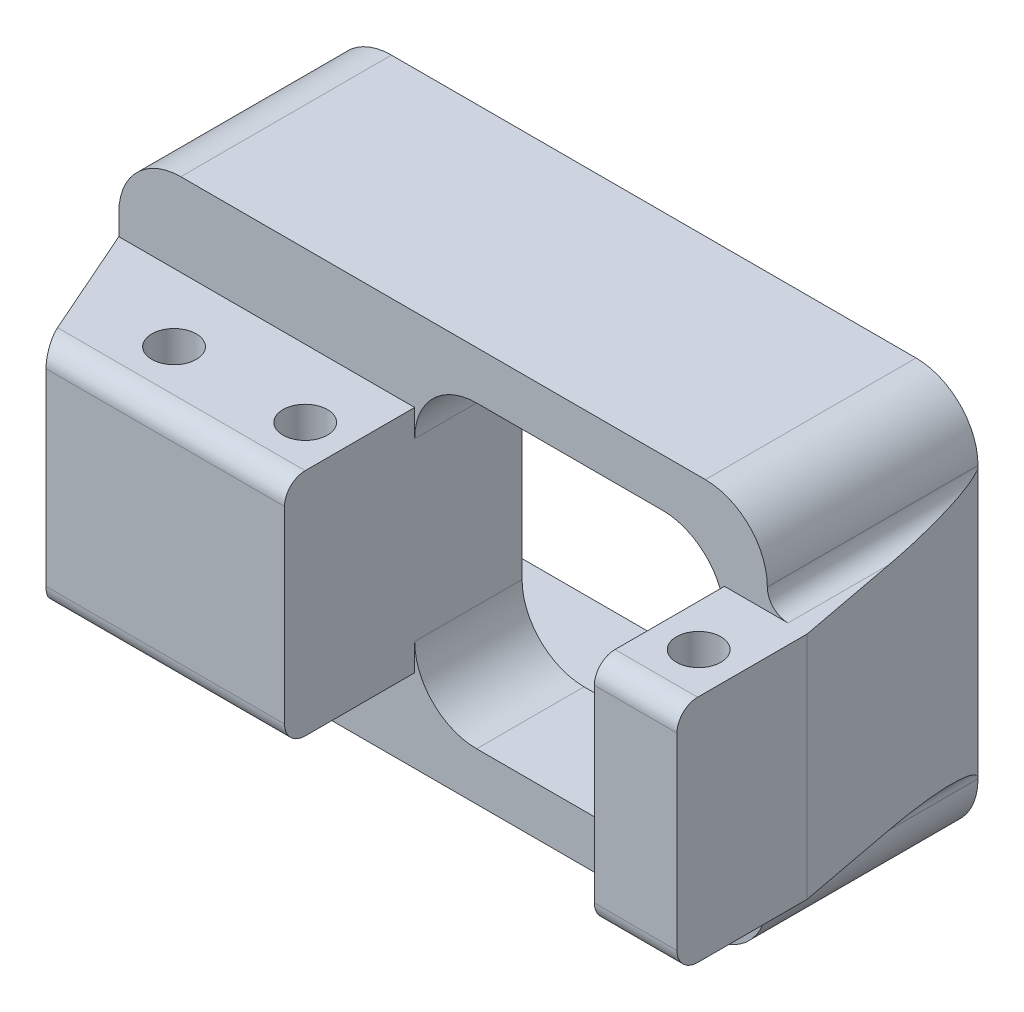
SolidWorks part; units mm, degrees
ref_plane "Front Plane" through (0, 0, 0) normal (0, 0, 1) x (1, 0, 0)
ref_plane "Top Plane" through (0, 0, 0) normal (0, 1, 0) x (1, 0, 0)
ref_plane "Right Plane" through (0, 0, 0) normal (1, 0, 0) x (0, 0, -1)
sketch "Sketch2" plane through (0, 0, 0) normal (0, 0, 1) x (1, 0, 0)
  line L1 (0, 0) -> (58, 0)
  line L2 (0, 0) -> (0, -33.5)
  line L3 (0, -33.5) -> (58, -33.5)
  line L4 (58, 0) -> (58, -33.5)
  line L5 (26.25, -2.25) -> (56.25, -2.25)
  line L6 (26.25, -2.25) -> (26.25, -31.25)
  line L7 (26.25, -31.25) -> (56.25, -31.25)
  line L8 (56.25, -2.25) -> (56.25, -31.25)
  line L9 (26.25, -2.25) -> (56.25, -31.25) construction
  line L10 (26.25, -31.25) -> (56.25, -2.25) construction
  line L11 (-2.4, 2.4) -> (60.4, 2.4)
  line L12 (-2.4, 2.4) -> (-2.4, -35.9)
  line L13 (-2.4, -35.9) -> (60.4, -35.9)
  line L14 (60.4, 2.4) -> (60.4, -35.9)
  circle A1 centre (16.2, -16.75) radius 4.25
  circle A2 centre (14.45, -16.75) radius 6
  circle A3 centre (14.45, -16.75) radius 6.5
  point P5 (41.25, -16.75)
  point P6 (41.25, -16.75)
  point P7 (16.2, -16.75)
  dimension "D9" = 8.5
  dimension "D10" = 12
  dimension "D15" = 13
  dimension "D16" = 1.75
  dimension "D1" = 33.5
  dimension "D2" = 58
  dimension "D3" = 16.75
  dimension "D4" = 16.75
  dimension "D5" = 16.2
  dimension "D6" = 16.75
  dimension "D7" = 30
  dimension "D8" = 29
  dimension "D11" = 2.4
  dimension "D12" = 2.4
  dimension "D13" = 2.4
  dimension "D14" = 2.4
extrude "Boss-Extrude1" add sketch "Sketch2" along normal blind 10 contours L14 L11 L12 L13 L1 L4 L3 L2 | L4 L1 L2 L3 A2 L5 L8 L7 L6 | A1 A2 | A3 A2 region at (29, -0.6698, 0) region at (29, 1.6644, 0) region at (8.6197, -16.75, 0) region at (8.1338, -16.75, 0)
extrude "Boss-Extrude2" add sketch "Sketch2<3>" against normal blind 10 contours L14 L11 L12 L13 L1 L4 L3 L2 region at (29, 1.6644, 0)
sketch "Sketch2<3>" plane through (0, 0, 0) normal (0, 0, 1) x (1, 0, 0) same geometry as "Sketch2"
extrude "Cut-Extrude1" cut sketch "Sketch2<4>" along normal blind 3 contours A3
sketch "Sketch2<4>" plane through (0, 0, 0) normal (0, 0, 1) x (1, 0, 0) same geometry as "Sketch2"
fillet "Fillet1" radius 3.6 4 edges at (58, -33.5, -5) (0, -33.5, -5) (0, 0, -5) (58, 0, -5)
fillet "Fillet2" radius 6 8 edges at (56.25, -31.25, 5) (26.25, -31.25, 5) (26.25, -2.25, 5) (56.25, -2.25, 5) (60.4, -35.9, 0) (-2.4, -35.9, 0) (-2.4, 2.4, 0) (60.4, 2.4, 0)
sketch "Sketch4" plane through (0, 0, 10) normal (0, 0, 1) x (1, 0, 0)
  line L0 (56.25, -8.25) -> (56.25, -25.25) construction
  line L1 (32.25, -31.25) -> (50.25, -31.25) construction
  line L2 (26.25, -8.25) -> (26.25, -25.25) construction
  line L3 (32.25, -2.25) -> (50.25, -2.25) construction
  line L4 (3.6, -35.9) -> (54.4, -35.9)
  line L5 (60.4, -29.9) -> (60.4, -3.6)
  line L6 (54.4, 2.4) -> (3.6, 2.4)
  line L7 (-2.4, -3.6) -> (-2.4, -29.9)
  line L8 (3.6, -35.9) -> (54.4, -35.9)
  line L9 (60.4, -29.9) -> (60.4, -3.6)
  line L10 (54.4, 2.4) -> (3.6, 2.4)
  line L11 (-2.4, -3.6) -> (-2.4, -29.9)
  line L12 (56.25, -8.25) -> (56.25, -25.25)
  line L13 (32.25, -31.25) -> (50.25, -31.25)
  line L14 (26.25, -8.25) -> (26.25, -25.25)
  line L15 (32.25, -2.25) -> (50.25, -2.25)
  arc A0 (56.25, -8.25) -> (50.25, -2.25) centre (50.25, -8.25) ccw construction
  arc A1 (50.25, -31.25) -> (56.25, -25.25) centre (50.25, -25.25) ccw construction
  arc A2 (26.25, -25.25) -> (32.25, -31.25) centre (32.25, -25.25) ccw construction
  arc A3 (32.25, -2.25) -> (26.25, -8.25) centre (32.25, -8.25) ccw construction
  arc A4 (54.4, -35.9) -> (60.4, -29.9) centre (54.4, -29.9) ccw
  arc A5 (60.4, -3.6) -> (54.4, 2.4) centre (54.4, -3.6) ccw
  arc A6 (3.6, 2.4) -> (-2.4, -3.6) centre (3.6, -3.6) ccw
  arc A7 (-2.4, -29.9) -> (3.6, -35.9) centre (3.6, -29.9) ccw
  arc A8 (54.4, -35.9) -> (60.4, -29.9) centre (54.4, -29.9) ccw
  arc A9 (60.4, -3.6) -> (54.4, 2.4) centre (54.4, -3.6) ccw
  arc A10 (3.6, 2.4) -> (-2.4, -3.6) centre (3.6, -3.6) ccw
  arc A11 (-2.4, -29.9) -> (3.6, -35.9) centre (3.6, -29.9) ccw
  circle A12 centre (16.2, -16.75) radius 4.25 construction
  arc A13 (56.25, -8.25) -> (50.25, -2.25) centre (50.25, -8.25) ccw
  arc A14 (50.25, -31.25) -> (56.25, -25.25) centre (50.25, -25.25) ccw
  arc A15 (26.25, -25.25) -> (32.25, -31.25) centre (32.25, -25.25) ccw
  arc A16 (32.25, -2.25) -> (26.25, -8.25) centre (32.25, -8.25) ccw
  circle A17 centre (16.2, -16.75) radius 4.25
  dimension "D1" = 0
extrude "Boss-Extrude3" add sketch "Sketch4" along normal blind 0.4
sketch "Sketch5" plane through (0, 0, 10.4) normal (0, 0, 1) x (1, 0, 0)
  line L1 (3.15, -5.625) -> (64.25, -5.625)
  line L2 (3.15, -5.625) -> (3.15, -27.875)
  line L3 (3.15, -27.875) -> (64.25, -27.875)
  line L4 (64.25, -5.625) -> (64.25, -27.875)
  line L5 (26.25, -25.25) -> (26.25, -8.25)
  line L6 (56.25, -25.25) -> (56.25, -8.25)
  line L7 (32.25, -31.25) -> (50.25, -31.25) construction
  line L8 (26.25, -8.25) -> (26.25, -5.625)
  line L9 (26.25, -25.25) -> (26.25, -27.875)
  line L10 (56.25, -25.25) -> (56.25, -27.875)
  line L11 (56.25, -8.25) -> (56.25, -5.625)
  arc A0 (50.25, -31.25) -> (56.25, -25.25) centre (50.25, -25.25) ccw construction
  arc A1 (26.25, -25.25) -> (32.25, -31.25) centre (32.25, -25.25) ccw construction
  arc A2 (56.25, -8.25) -> (50.25, -2.25) centre (50.25, -8.25) ccw construction
  arc A3 (32.25, -2.25) -> (26.25, -8.25) centre (32.25, -8.25) ccw construction
  arc A4 (55.6453, -27.875) -> (56.25, -25.25) centre (50.25, -25.25) ccw
  arc A5 (26.25, -25.25) -> (26.8547, -27.875) centre (32.25, -25.25) ccw
  arc A6 (56.25, -8.25) -> (55.6453, -5.625) centre (50.25, -8.25) ccw
  arc A7 (26.8547, -5.625) -> (26.25, -8.25) centre (32.25, -8.25) ccw
  circle A8 centre (16.2, -16.75) radius 4.25
  point P0 (16.2, -16.75)
  point P6 (41.25, -16.75)
  point P7 (26.8547, -27.875)
  point P8 (55.6554, -27.875)
  point P10 (55.6453, -5.625)
  point P26 (26.8547, -5.625)
  arc M6 (50.25, -2.25) -> (56.25, -8.25) centre (50.25, -8.25) cw
  line M7 (56.25, -8.25) -> (56.25, -25.25)
  arc M8 (56.25, -25.25) -> (50.25, -31.25) centre (50.25, -25.25) cw
  arc M10 (32.25, -31.25) -> (26.25, -25.25) centre (32.25, -25.25) cw
  line M11 (26.25, -25.25) -> (26.25, -8.25)
  arc M12 (26.25, -8.25) -> (32.25, -2.25) centre (32.25, -8.25) cw
  line M16 (60.4, -29.9) -> (60.4, -3.6)
  circle M21 centre (16.2, -16.75) radius 4.25
  dimension "D1" = 38.1
  dimension "D2" = 14.5
  dimension "D3" = 11.125
  dimension "D4" = 22.25
  dimension "D5" = 8
  dimension "D6" = 3.15
extrude "Boss-Extrude4" add sketch "Sketch5" along normal blind 12.6 contours L2 L3 L1 M10 M11 M12 M21 | L3 L1 M8 M16 M6 M7 | L4 L1 L3 M16 | M21 region at (14.7, -5.9457, 10.4) region at (58.325, -16.75, 10.4) region at (62.325, -16.75, 10.4) region at (16.2, -16.75, 10.4)
sketch "Sketch6" plane through (0, -5.625, 0) normal (0, 1, 0) x (1, 0, 0)
  line L0 (3.15, -23) -> (3.15, -10.4) construction
  line L1 (3.15, -10.4) -> (26.25, -10.4) construction
  circle A0 centre (9.5, -16.95) radius 2.15
  circle A1 centre (22.2, -16.95) radius 2.15
  circle A2 centre (60.3, -16.95) radius 2.15
  dimension "D5" = 4.3
  dimension "D1" = 12.7
  dimension "D2" = 38.1
  dimension "D3" = 6.35
  dimension "D4" = 6.55
extrude "Cut-Extrude2" cut sketch "Sketch6" against normal up to surface (22.25 mm away) up to face at (14.7, -27.875, 16.7)
sketch "Sketch7" plane through (0, -5.625, 0) normal (0, 1, 0) x (1, 0, 0)
  line L0 (3.15, -23) -> (3.15, -10.4)
  line L1 (3.15, -10.4) -> (-2.4, -10.4)
  line L2 (-2.4, -10.4) -> (3.15, -23)
  line L3 (64.25, -10.4) -> (60.4, -10.4)
  line L4 (60.4, -10.4) -> (60.4, 10)
  line L5 (60.4, 10) -> (64.25, -10.4)
  line M4 (3.15, -10.4) -> (3.15, -23)
extrude "Boss-Extrude6" add sketch "Sketch7" against normal up to surface (22.25 mm away) contours L5 L4 L3 | L1 L2 M4 region at (1.3, -5.625, 14.6) region at (61.6833, -5.625, 3.6) up to face at (9.5, -27.875, 19.1)
fillet "Fillet5" radius 2 2 edges at (60.4, -27.875, 0.2) (60.4, -5.625, 0.2)
fillet "Fillet6" radius 2 4 edges at (60.25, -27.875, 23) (14.7, -27.875, 23) (60.25, -5.625, 23) (14.7, -5.625, 23)
extrude "Cut-Extrude3" cut sketch "Sketch4<2>" along normal blind 5 contours A17
sketch "Sketch4<2>" plane through (0, 0, 10) normal (0, 0, 1) x (1, 0, 0) same geometry as "Sketch4"
fillet "Fillet7" radius 1 1 edges at (20.45, -16.75, 15)
